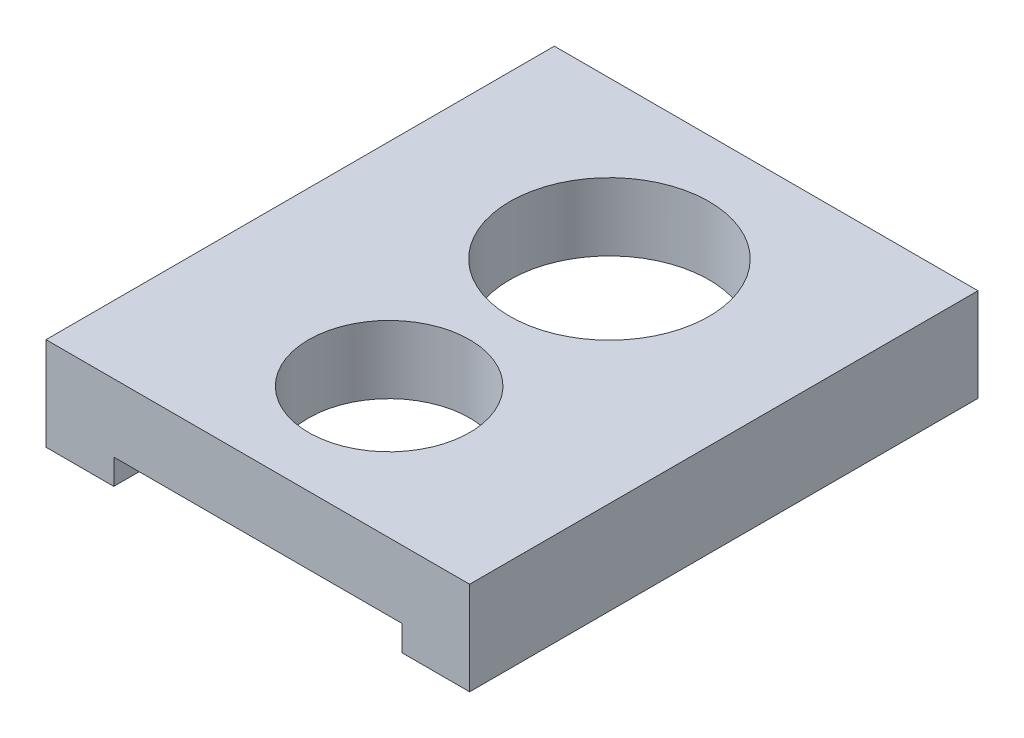
SolidWorks part; units mm, degrees
material "6061 合金"
ref_plane "前基準面" through (0, 0, 0) normal (0, 0, 1) x (1, 0, 0)
ref_plane "上基準面" through (0, 0, 0) normal (0, 1, 0) x (1, 0, 0)
ref_plane "右基準面" through (0, 0, 0) normal (1, 0, 0) x (0, 0, -1)
sketch "草圖1" plane through (0, 0, 0) normal (0, 0, 1) x (1, 0, 0)
  line L0 (-25, 0) -> (-17, 0)
  line L1 (-17, 0) -> (-17, 3)
  line L2 (-17, 3) -> (17, 3)
  line L3 (17, 3) -> (17, 0)
  line L4 (17, 0) -> (25, 0)
  line L5 (25, 0) -> (25, 11)
  line L6 (25, 11) -> (-25, 11)
  line L7 (-25, 11) -> (-25, 0)
  point P3 (0, 3)
  dimension "D1" = 3
  dimension "D2" = 11
  dimension "D3" = 8
  dimension "D4" = 50
extrude "填料-伸長1" add sketch "草圖1" along normal blind 60
sketch "草圖2" plane through (0, 11, 0) normal (0, 1, 0) x (1, 0, 0)
  line L0 (25, 0) -> (-25, 0) construction
  circle A0 centre (0, -18.5) radius 11.75
  point P5 (0, 0)
  dimension "D2" = 23.5
  dimension "D1" = 18.5
extrude "除料-伸長1" cut sketch "草圖2" against normal blind 40
sketch "草圖3" plane through (0, 11, 0) normal (0, 1, 0) x (1, 0, 0)
  line L0 (25, 0) -> (-25, 0) construction
  circle A0 centre (0, -44.5) radius 9.5
  circle A1 centre (0, -18.5) radius 11.75 construction
  point P7 (0, 0)
  dimension "D1" = 26
  dimension "D2" = 19
extrude "除料-伸長2" cut sketch "草圖3" against normal blind 40
